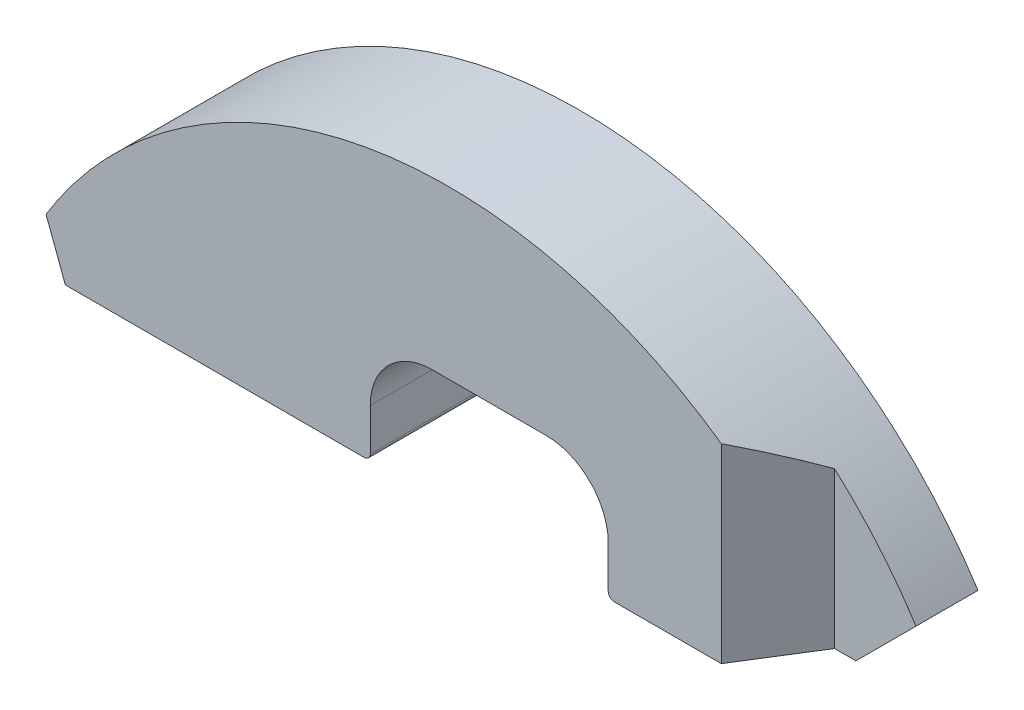
SolidWorks part; units mm, degrees
material "Polyurethane Foam Rigid"
ref_plane "Front Plane" through (0, 0, 0) normal (0, 0, 1) x (1, 0, 0)
ref_plane "Top Plane" through (0, 0, 0) normal (0, 1, 0) x (1, 0, 0)
ref_plane "Right Plane" through (0, 0, 0) normal (1, 0, 0) x (0, 0, -1)
sketch "Sketch1" plane through (0, 0, 0) normal (0, 0, 1) x (1, 0, 0)
  point P0 (0, 45.106)
  line B0 (-48.768, 0) -> (-48.768, 45.106)
  line B1 (-48.768, 45.106) -> (48.768, 45.106)
  line B2 (48.768, 0) -> (48.768, 45.106)
  line B3 (-48.768, 0) -> (-192.96, 0)
  line B4 (48.768, 0) -> (159.8172, 0)
  arc B5 (-192.96, 0) -> (159.8172, 0) centre (-16.5714, -80.3119) cw
sketch_block_instance "splash_guards-1"
sketch_block "splash_guards"
extrude "Boss-Extrude1" add sketch "Sketch1" along normal blind 53.975
fillet "Fillet1" radius 25.4 2 edges at (48.768, 45.106, 26.9875) (-48.768, 45.106, 26.9875)
fillet "Fillet2" radius 2.54 2 edges at (-48.768, 0, 26.9875) (48.768, 0, 26.9875)
chamfer "Chamfer1" distance 38.1 angle 45 1 edges at (159.8172, 0, 26.9875) first distance on face at (105.5626, 0, 26.9875)
chamfer "Chamfer2" distance 25.4 angle 45 1 edges at (-192.96, 0, 26.9875) first distance on face at (-26.955, 62.6564, 26.9875)
sketch "Sketch2" plane through (0, 0, 0) normal (0, 1, 0) x (1, 0, 0)
  line L0 (112.9686, -25.4) -> (49.4686, -127) construction
  line L1 (163.7686, -25.4) -> (112.9686, -25.4) construction
  line L2 (112.9686, -25.4) -> (49.4686, -127)
  line L3 (163.7686, -25.4) -> (112.9686, -25.4)
  line L4 (163.7686, -25.4) -> (163.7686, -127)
  line L5 (163.7686, -127) -> (49.4686, -127)
extrude "Cut-Extrude2" cut sketch "Sketch2" along normal through all
